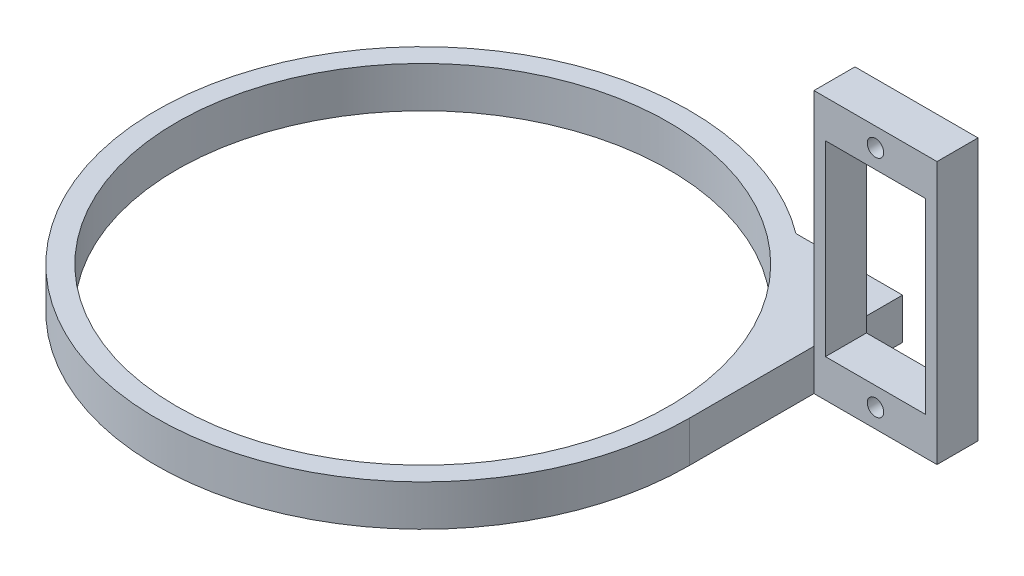
SolidWorks part; units mm, degrees
ref_plane "Front Plane" through (0, 0, 0) normal (0, 0, 1) x (1, 0, 0)
ref_plane "Top Plane" through (0, 0, 0) normal (0, 1, 0) x (1, 0, 0)
ref_plane "Right Plane" through (0, 0, 0) normal (1, 0, 0) x (0, 0, -1)
sketch "Sketch1" plane through (0, 0, 0) normal (0, 1, 0) x (1, 0, 0)
  line L0 (32.5, 0) -> (32.5, 26)
  line L1 (32.5, 26) -> (19.5, 26)
  circle A0 centre (0, 0) radius 30
  arc A1 (19.5, 26) -> (32.5, 0) centre (0, 0) ccw
  dimension "D1" = 60
  dimension "D2" = 65
  dimension "D3" = 26
extrude "Boss-Extrude1" add sketch "Sketch1" along normal blind 5
sketch "Sketch3" plane through (0, 0, 0) normal (0, 0, 1) x (1, 0, 0)
  line L0 (32.5, 0) -> (32.5, 32)
  line L1 (32.5, 32) -> (47.5, 32)
  line L2 (47.5, 32) -> (47.5, 0)
  line L3 (47.5, 0) -> (32.5, 0)
  line L4 (40, 32) -> (40, 29.7) construction
  line L5 (32.5, 16) -> (47.5, 16) construction
  line L7 (33.9, 4.6) -> (46.1, 4.6)
  line L8 (33.9, 4.6) -> (33.9, 27.4)
  line L9 (33.9, 27.4) -> (46.1, 27.4)
  line L10 (46.1, 4.6) -> (46.1, 27.4)
  line L11 (33.9, 4.6) -> (46.1, 27.4) construction
  line L12 (33.9, 27.4) -> (46.1, 4.6) construction
  circle A0 centre (40, 29.7) radius 1
  circle A1 centre (40, 2.3) radius 1
  point P12 (40, 16)
  dimension "D4" = 2
  dimension "D1" = 32
  dimension "D2" = 15
  dimension "D3" = 2.3
  dimension "D5" = 22.8
  dimension "D6" = 12.2
extrude "Boss-Extrude4" add sketch "Sketch3" along normal blind 5 from offset 20.2 offset against normal yes
